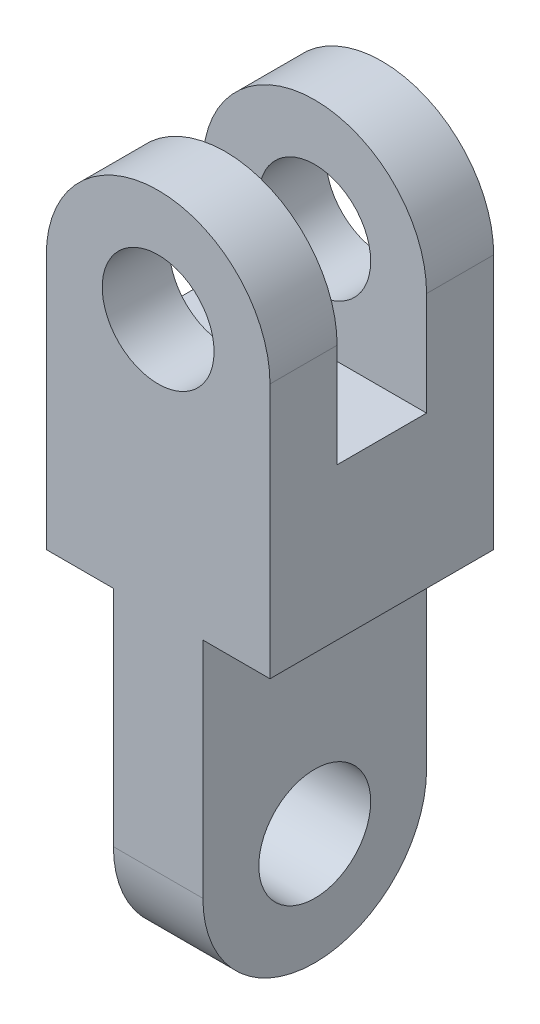
SolidWorks part; units mm, degrees
ref_plane "Front Plane" through (0, 0, 0) normal (0, 0, 1) x (1, 0, 0)
ref_plane "Top Plane" through (0, 0, 0) normal (0, 1, 0) x (1, 0, 0)
ref_plane "Right Plane" through (0, 0, 0) normal (1, 0, 0) x (0, 0, -1)
sketch "Sketch1" plane through (0, 0, 0) normal (0, 0, 1) x (1, 0, 0)
  line L0 (20, 0) -> (50, 0)
  line L1 (50, 0) -> (50, 114.1216)
  line L2 (-50, 114.1216) -> (-50, 0)
  line L3 (-50, 0) -> (-20, 0)
  line L4 (-20, 0) -> (-20, -100)
  line L5 (-20, -100) -> (20, -100)
  line L6 (20, -100) -> (20, 0)
  arc A0 (50, 114.1216) -> (-50, 114.1216) centre (0, 114.1216) ccw
  dimension "D5" = 100
  dimension "D1" = 30
  dimension "D2" = 30
  dimension "D3" = 40
  dimension "D4" = 20
extrude "Boss-Extrude1" add sketch "Sketch1" along normal blind 50 and the other way blind 50
sketch "Sketch4" plane through (50, 0, 0) normal (1, 0, 0) x (0, 0, -1)
  line L0 (-20, 114.1216) -> (-20, 67.8479)
  line L1 (50, 114.1216) -> (-50, 114.1216) construction
  line L2 (-20, 67.8479) -> (20, 67.8479)
  line L3 (20, 67.8479) -> (20, 168.6629)
  line L4 (20, 168.6629) -> (-20, 168.6629)
  line L5 (-20, 168.6629) -> (-20, 114.1216)
  line L6 (50, 0) -> (50, 114.1216) construction
  line L7 (-50, 0) -> (-50, 114.1216) construction
  dimension "D1" = 30
  dimension "D2" = 30
extrude "Cut-Extrude1" cut sketch "Sketch4" against normal through all
hole_wizard "Ø25.0 (50) Diameter Hole1" positions "Sketch5" profile "Sketch6" hole size "Ø25.0" standard "ANSI Metric" end condition through all
sketch "Sketch5" plane through (0, 0, 50) normal (0, 0, 1) x (1, 0, 0)
  point P0 (0, 114.1216)
  point P3 (0, 114.1216)
sketch "Sketch6" plane through (0, 114.1216, 50) normal (1, 0, 0) x (0, -1, 0)
  line L0 (0, 0) -> (0, 100)
  line L1 (0, 100) -> (25, 100)
  line L2 (25, 100) -> (25, 0)
  line L5 (25, 0) -> (0, 0)
  line L11 (0, -6.35) -> (0, 107.95) construction
  dimension "Thru Hole Dia." = 50
  dimension "Thru Hole Depth" = 100
sketch "Sketch7" plane through (0, -100, 0) normal (0, -1, 0) x (1, 0, 0)
  line L0 (20, 50) -> (20, 0)
  line L1 (20, -50) -> (20, 50) construction
  line L2 (20, 0) -> (-20, 0)
  line L3 (-20, -50) -> (-20, 50) construction
  line L4 (-20, 0) -> (-20, 50)
  line L5 (-20, 50) -> (20, 50)
revolve "Revolve1" add sketch "Sketch7" angle 180 about L2 reverse direction yes
hole_wizard "Ø1.0 (50) Diameter Hole1" positions "Sketch8" profile "Sketch9" hole size "Ø1.0" standard "ANSI Metric" end condition through all
sketch "Sketch8" plane through (20, 0, 0) normal (1, 0, 0) x (0, 0, -1)
  point P0 (0, -100)
sketch "Sketch9" plane through (20, -100, 0) normal (0, 1, 0) x (0, 0, -1)
  line L0 (0, 0) -> (0, 70)
  line L1 (0, 70) -> (25, 70)
  line L2 (25, 70) -> (25, 0)
  line L5 (25, 0) -> (0, 0)
  line L11 (0, -6.35) -> (0, 107.95) construction
  dimension "Thru Hole Dia." = 50
  dimension "Thru Hole Depth" = 70
